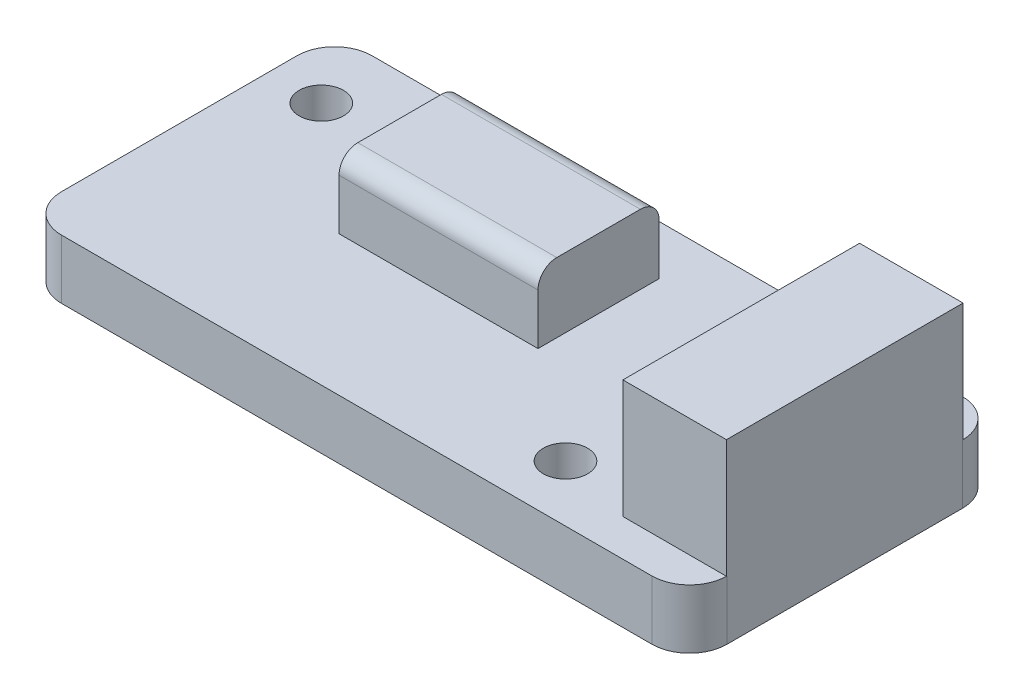
SolidWorks part; units mm, degrees
ref_plane "Front Plane" through (0, 0, 0) normal (0, 0, 1) x (1, 0, 0)
ref_plane "Top Plane" through (0, 0, 0) normal (0, 1, 0) x (1, 0, 0)
ref_plane "Right Plane" through (0, 0, 0) normal (1, 0, 0) x (0, 0, -1)
sketch "Sketch1" plane through (0, 0, 0) normal (0, 1, 0) x (1, 0, 0)
  line L1 (-19.96, -10.5) -> (19.96, -10.5)
  line L2 (-22.5, -7.96) -> (-22.5, 7.96)
  line L3 (-19.96, 10.5) -> (19.96, 10.5)
  line L4 (22.5, -7.96) -> (22.5, 7.96)
  line L5 (-22.5, -10.5) -> (22.5, 10.5) construction
  line L6 (-22.5, 10.5) -> (22.5, -10.5) construction
  arc A0 (19.96, 10.5) -> (22.5, 7.96) centre (19.96, 7.96) cw
  arc A1 (19.96, -10.5) -> (22.5, -7.96) centre (19.96, -7.96) ccw
  arc A2 (-19.96, -10.5) -> (-22.5, -7.96) centre (-19.96, -7.96) cw
  arc A3 (-22.5, 7.96) -> (-19.96, 10.5) centre (-19.96, 7.96) cw
  point P0 (0, 0)
  dimension "D3" = 2.54
  dimension "D1" = 45
  dimension "D2" = 21
extrude "Boss-Extrude1" add sketch "Sketch1" along normal blind 4
sketch "Sketch2" plane through (0, 4, 0) normal (0, 1, 0) x (1, 0, 0)
  line L0 (-22.5, 0) -> (22.5, 0) construction
  line L1 (22.5, -7.96) -> (22.5, 7.96) construction
  line L3 (15.5, -8) -> (22.5, -8)
  line L4 (15.5, -8) -> (15.5, 8)
  line L5 (15.5, 8) -> (22.5, 8)
  line L6 (22.5, -8) -> (22.5, 8)
  line L7 (15.5, -8) -> (22.5, 8) construction
  line L8 (15.5, 8) -> (22.5, -8) construction
  point P0 (19, 0)
  point P6 (0, 0)
  dimension "D1" = 16
  dimension "D2" = 7
  dimension "D3" = 0
extrude "Boss-Extrude2" add sketch "Sketch2" along normal blind 8
sketch "Sketch3" plane through (0, 4, 0) normal (0, 1, 0) x (1, 0, 0)
  line L1 (-10.6548, 7.1542) -> (2.7975, 7.1542)
  line L2 (-10.6548, 7.1542) -> (-10.6548, -1.0395)
  line L3 (-10.6548, -1.0395) -> (2.7975, -1.0395)
  line L4 (2.7975, 7.1542) -> (2.7975, -1.0395)
extrude "Boss-Extrude3" add sketch "Sketch3" along normal blind 4.698
fillet "Fillet1" radius 1.27 2 edges at (-3.9287, 8.698, -7.1542) (-3.9287, 8.698, 1.0395)
sketch "Sketch4" plane through (0, 4, 0) normal (0, 1, 0) x (1, 0, 0)
  line L0 (-19.96, -10.5) -> (19.96, -10.5) construction
  line L1 (-18.902, -6.69) -> (10.308, -6.69) construction
  line L2 (-18.902, -6.69) -> (-18.902, 6.01) construction
  line L3 (-18.902, 6.01) -> (10.308, 6.01) construction
  line L4 (10.308, -6.69) -> (10.308, 6.01) construction
  line L5 (-18.902, -6.69) -> (10.308, 6.01) construction
  line L6 (-18.902, 6.01) -> (10.308, -6.69) construction
  line L7 (22.5, -7.96) -> (22.5, 7.96) construction
  circle A0 centre (-18.902, 6.01) radius 1.5
  circle A3 centre (10.308, -6.69) radius 1.5
  point P0 (-4.297, -0.34)
  dimension "D5" = 3
  dimension "D8" = 3
  dimension "D1" = 29.21
  dimension "D2" = 12.7
  dimension "D3" = 3.81
  dimension "D4" = 12.192
extrude "Cut-Extrude1" cut sketch "Sketch4" against normal through all
